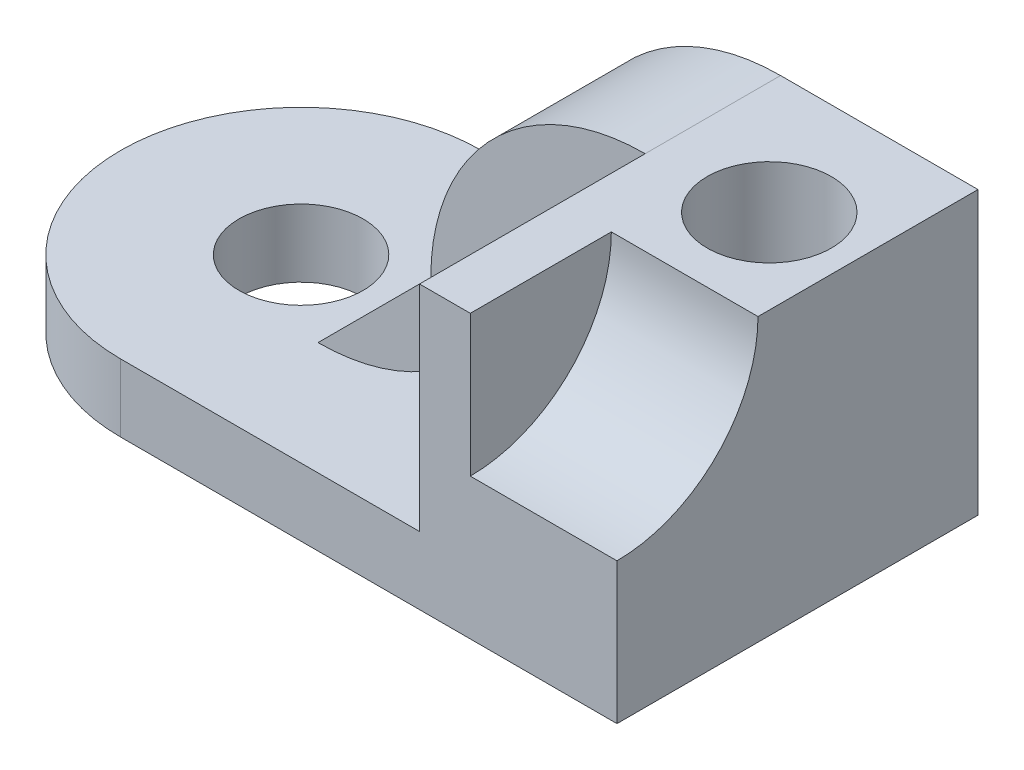
SolidWorks part; units mm, degrees
ref_plane "Front Plane" through (0, 0, 0) normal (0, 0, 1) x (1, 0, 0)
ref_plane "Top Plane" through (0, 0, 0) normal (0, 1, 0) x (1, 0, 0)
ref_plane "Right Plane" through (0, 0, 0) normal (1, 0, 0) x (0, 0, -1)
sketch "Sketch1" plane through (0, 0, 0) normal (0, 0, 1) x (1, 0, 0)
  line L0 (85, 12) -> (47, 12)
  line L1 (0, 0) -> (120, 0)
  line L2 (0, 0) -> (0, 12)
  line L3 (0, 12) -> (120, 12)
  line L4 (120, 0) -> (120, 12)
  line L5 (120, 12) -> (85, 12)
  line L6 (120, 12) -> (120, 50)
  line L7 (120, 50) -> (85, 50)
  line L8 (85, 12) -> (85, 50)
  line L9 (94, 50) -> (120, 50)
  line L10 (94, 50) -> (94, 25)
  line L11 (94, 25) -> (120, 25)
  line L12 (120, 50) -> (120, 25)
  line L13 (47, 12) -> (85, 50) construction
  arc A0 (47, 12) -> (85, 50) centre (85, 12) cw
  arc A2 (85, 50) -> (47, 12) centre (47, 50) cw
  dimension "D5" = 35
  dimension "D7" = 38
  dimension "D8" = 25
  dimension "D1" = 120
  dimension "D2" = 50
  dimension "D3" = 12
  dimension "D4" = 38
  dimension "D6" = 26
extrude "Boss-Extrude1" add sketch "Sketch1" along normal mid plane 64 contours L1 L4 L3 L0 L2 | L11 L10 L7 L8 L3 L6 | L10 L11 L6 L7 region at (60, 6, 0) region at (98.1985, 24.7868, 0) region at (107, 37.5, 0)
extrude "Boss-Extrude2" add sketch "Sketch1<3>" along normal blind 24 from surface separate body contours A0 L13 region at (62.8088, 34.1912, 0) starting at face at (68.3333, 20.6667, -32)
sketch "Sketch1<3>" plane through (0, 0, 0) normal (0, 0, 1) x (1, 0, 0) same geometry as "Sketch1"
extrude "Boss-Extrude3" add sketch "Sketch1<4>" along normal blind 44 from surface separate body contours L13 A2 region at (69.1912, 27.8088, 0) starting at face at (68.3333, 20.6667, -32)
sketch "Sketch1<4>" plane through (0, 0, 0) normal (0, 0, 1) x (1, 0, 0) same geometry as "Sketch1"
sketch "Sketch2" plane through (120, 0, 0) normal (1, 0, 0) x (0, 0, -1)
  circle A0 centre (-32, 50) radius 25
extrude "Cut-Extrude2" cut sketch "Sketch2" against normal blind 26
sketch "Sketch3" plane through (0, 12, 0) normal (0, 1, 0) x (1, 0, 0)
  line L0 (0, 0) -> (32, 0) construction
  circle A0 centre (32, 0) radius 11
  dimension "D1" = 22
extrude "Cut-Extrude3" cut sketch "Sketch3" against normal through all
fillet "Fillet1" radius 32 2 edges at (0, 6, 32) (0, 6, -32)
sketch "Sketch4" plane through (0, 50, 0) normal (0, 1, 0) x (1, 0, 0)
  line L0 (105, 32) -> (105, 10) construction
  line L1 (120, 32) -> (85, 32) construction
  circle A0 centre (105, 10) radius 11
  dimension "D1" = 22
  dimension "D2" = 15
extrude "Cut-Extrude4" cut sketch "Sketch4" against normal through all
